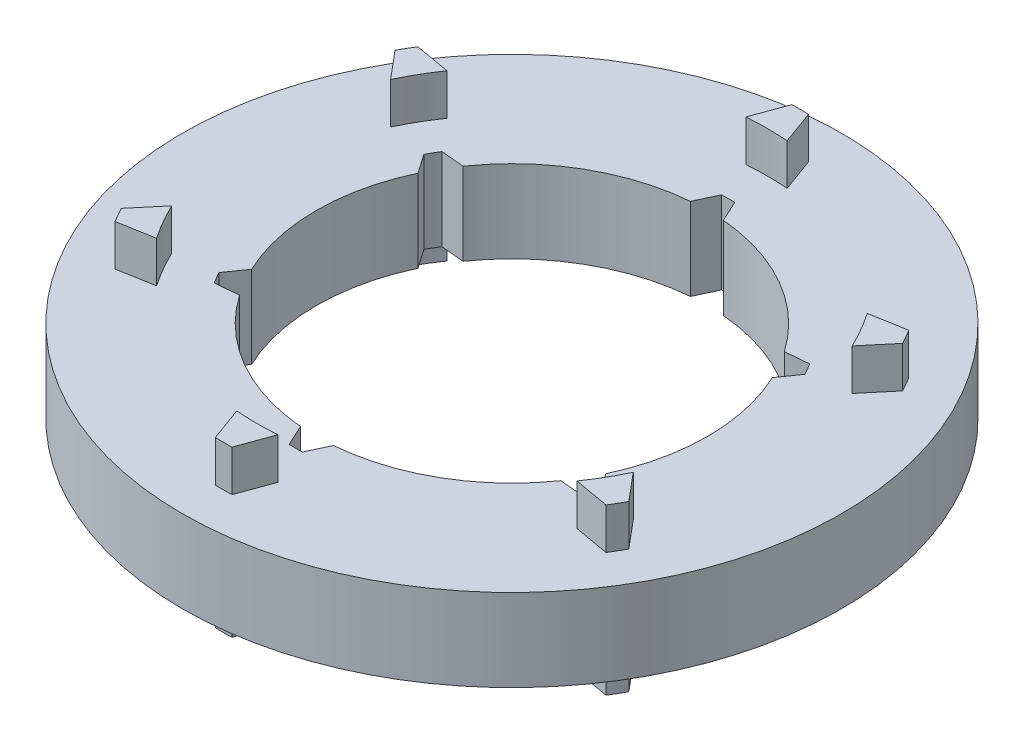
SolidWorks part; units mm, degrees
ref_plane "Front Plane" through (0, 0, 0) normal (0, 0, 1) x (1, 0, 0)
ref_plane "Top Plane" through (0, 0, 0) normal (0, 1, 0) x (1, 0, 0)
ref_plane "Right Plane" through (0, 0, 0) normal (1, 0, 0) x (0, 0, -1)
sketch "Sketch1" plane through (0, 0, 0) normal (0, 1, 0) x (1, 0, 0)
  line L0 (0, 0) -> (0, 34.5685) construction
  line L1 (-2, 26.1737) -> (-2, 23.6656) construction
  line L2 (-2, 23.6656) -> (-0.8006, 26.2378)
  line L3 (2, 23.6656) -> (0.8006, 26.2378)
  line L4 (19.495, 13.5649) -> (22.3223, 13.8122)
  line L5 (21.495, 10.1008) -> (23.1229, 12.4256)
  line L6 (21.495, -10.1008) -> (23.1229, -12.4256)
  line L7 (19.495, -13.5649) -> (22.3223, -13.8122)
  line L8 (2, -23.6656) -> (0.8006, -26.2378)
  line L9 (-2, -23.6656) -> (-0.8006, -26.2378)
  line L10 (-19.495, -13.5649) -> (-22.3223, -13.8122)
  line L11 (-21.495, -10.1008) -> (-23.1229, -12.4256)
  line L12 (-21.495, 10.1008) -> (-23.1229, 12.4256)
  line L13 (-19.495, 13.5649) -> (-22.3223, 13.8122)
  arc A0 (-2, 23.6656) -> (-19.495, 13.5649) centre (0, 0) ccw
  arc A1 (0.8006, 26.2378) -> (-0.8006, 26.2378) centre (0, 0) ccw
  arc A2 (23.1229, 12.4256) -> (22.3223, 13.8122) centre (0, 0) ccw
  arc A3 (22.3223, -13.8122) -> (23.1229, -12.4256) centre (0, 0) ccw
  arc A4 (-0.8006, -26.2378) -> (0.8006, -26.2378) centre (0, 0) ccw
  arc A5 (-23.1229, -12.4256) -> (-22.3223, -13.8122) centre (0, 0) ccw
  arc A6 (-22.3223, 13.8122) -> (-23.1229, 12.4256) centre (0, 0) ccw
  arc A7 (-21.495, 10.1008) -> (-21.495, -10.1008) centre (0, 0) ccw
  arc A8 (19.495, 13.5649) -> (2, 23.6656) centre (0, 0) ccw
  arc A9 (21.495, -10.1008) -> (21.495, 10.1008) centre (0, 0) ccw
  arc A10 (2, -23.6656) -> (19.495, -13.5649) centre (0, 0) ccw
  arc A11 (-19.495, -13.5649) -> (-2, -23.6656) centre (0, 0) ccw
  circle A12 centre (0, 0) radius 40
  point P30 (0, 0)
  dimension "D1" = 47.5
  dimension "D2" = 52.5
  dimension "D6" = 80
  dimension "D3" = 2
  dimension "D4" = 25
  dimension "D5" = 6
extrude "Boss-Extrude1" add sketch "Sketch1" along normal blind 10
sketch "4,5,6" [suppressed] plane through (0, 10, 0) normal (0, 1, 0) x (1, 0, 0)
  line L0 (0, 23.5241) -> (0, 36.2824) construction
  line L1 (2.5, 35.9681) -> (2.5, 28.892) construction
  line L2 (2.5, 28.892) -> (1.0105, 32.9845)
  line L3 (-2.5, 28.892) -> (-1.0105, 32.9845)
  line L4 (23.7712, 16.6111) -> (28.0602, 17.3673)
  line L5 (26.2712, 12.281) -> (29.0707, 15.6172)
  line L6 (26.2712, -12.281) -> (29.0707, -15.6172)
  line L7 (23.7712, -16.6111) -> (28.0602, -17.3673)
  line L8 (2.5, -28.892) -> (1.0105, -32.9845)
  line L9 (-2.5, -28.892) -> (-1.0105, -32.9845)
  line L10 (-23.7712, -16.6111) -> (-28.0602, -17.3673)
  line L11 (-26.2712, -12.281) -> (-29.0707, -15.6172)
  line L12 (-26.2712, 12.281) -> (-29.0707, 15.6172)
  line L13 (-23.7712, 16.6111) -> (-28.0602, 17.3673)
  arc A0 (2.5, 28.892) -> (-2.5, 28.892) centre (0, 0) ccw
  arc A1 (1.0105, 32.9845) -> (-1.0105, 32.9845) centre (0, 0) ccw
  arc A2 (26.2712, 12.281) -> (23.7712, 16.6111) centre (0, 0) ccw
  arc A3 (29.0707, 15.6172) -> (28.0602, 17.3673) centre (0, 0) ccw
  arc A4 (23.7712, -16.6111) -> (26.2712, -12.281) centre (0, 0) ccw
  arc A5 (28.0602, -17.3673) -> (29.0707, -15.6172) centre (0, 0) ccw
  arc A6 (-2.5, -28.892) -> (2.5, -28.892) centre (0, 0) ccw
  arc A7 (-1.0105, -32.9845) -> (1.0105, -32.9845) centre (0, 0) ccw
  arc A8 (-26.2712, -12.281) -> (-23.7712, -16.6111) centre (0, 0) ccw
  arc A9 (-29.0707, -15.6172) -> (-28.0602, -17.3673) centre (0, 0) ccw
  arc A10 (-23.7712, 16.6111) -> (-26.2712, 12.281) centre (0, 0) ccw
  arc A11 (-28.0602, 17.3673) -> (-29.0707, 15.6172) centre (0, 0) ccw
  point P31 (0, 0)
  dimension "D1" = 58
  dimension "D2" = 66
  dimension "D3" = 2.5
  dimension "D4" = 20
  dimension "D5" = 6
sketch "1,2,3" plane through (0, 10, 0) normal (0, 1, 0) x (1, 0, 0)
  line L0 (0, 18.8714) -> (0, 44.4172) construction
  line L1 (2.5, 34.9106) -> (2.5, 30.899) construction
  line L2 (2.5, 30.899) -> (1.0127, 34.9853)
  line L3 (-2.5, 30.899) -> (-1.0127, 34.9853)
  line L4 (25.5093, 17.6146) -> (29.7918, 18.3697)
  line L5 (28.0093, 13.2845) -> (30.8045, 16.6156)
  line L6 (28.0093, -13.2845) -> (30.8045, -16.6156)
  line L7 (25.5093, -17.6146) -> (29.7918, -18.3697)
  line L8 (2.5, -30.899) -> (1.0127, -34.9853)
  line L9 (-2.5, -30.899) -> (-1.0127, -34.9853)
  line L10 (-25.5093, -17.6146) -> (-29.7918, -18.3697)
  line L11 (-28.0093, -13.2845) -> (-30.8045, -16.6156)
  line L12 (-28.0093, 13.2845) -> (-30.8045, 16.6156)
  line L13 (-25.5093, 17.6146) -> (-29.7918, 18.3697)
  arc A0 (2.5, 30.899) -> (-2.5, 30.899) centre (0, 0) ccw
  arc A1 (1.0127, 34.9853) -> (-1.0127, 34.9853) centre (0, 0) ccw
  arc A2 (28.0093, 13.2845) -> (25.5093, 17.6146) centre (0, 0) ccw
  arc A3 (30.8045, 16.6156) -> (29.7918, 18.3697) centre (0, 0) ccw
  arc A4 (25.5093, -17.6146) -> (28.0093, -13.2845) centre (0, 0) ccw
  arc A5 (29.7918, -18.3697) -> (30.8045, -16.6156) centre (0, 0) ccw
  arc A6 (-2.5, -30.899) -> (2.5, -30.899) centre (0, 0) ccw
  arc A7 (-1.0127, -34.9853) -> (1.0127, -34.9853) centre (0, 0) ccw
  arc A8 (-28.0093, -13.2845) -> (-25.5093, -17.6146) centre (0, 0) ccw
  arc A9 (-30.8045, -16.6156) -> (-29.7918, -18.3697) centre (0, 0) ccw
  arc A10 (-25.5093, 17.6146) -> (-28.0093, 13.2845) centre (0, 0) ccw
  arc A11 (-29.7918, 18.3697) -> (-30.8045, 16.6156) centre (0, 0) ccw
  point P32 (0, 0)
  dimension "D1" = 62
  dimension "D2" = 70
  dimension "D3" = 2.5
  dimension "D4" = 20
  dimension "D5" = 6
extrude "Boss-Extrude2" [suppressed] add sketch "4,5,6" along normal blind 5
extrude "Boss-Extrude4" add sketch "1,2,3" against normal blind 5 from surface starting at face at (0, 0, 40)
extrude "Boss-Extrude5" add sketch "1,2,3<2>" along normal blind 5
sketch "1,2,3<2>" plane through (0, 10, 0) normal (0, 1, 0) x (1, 0, 0) same geometry as "1,2,3"
